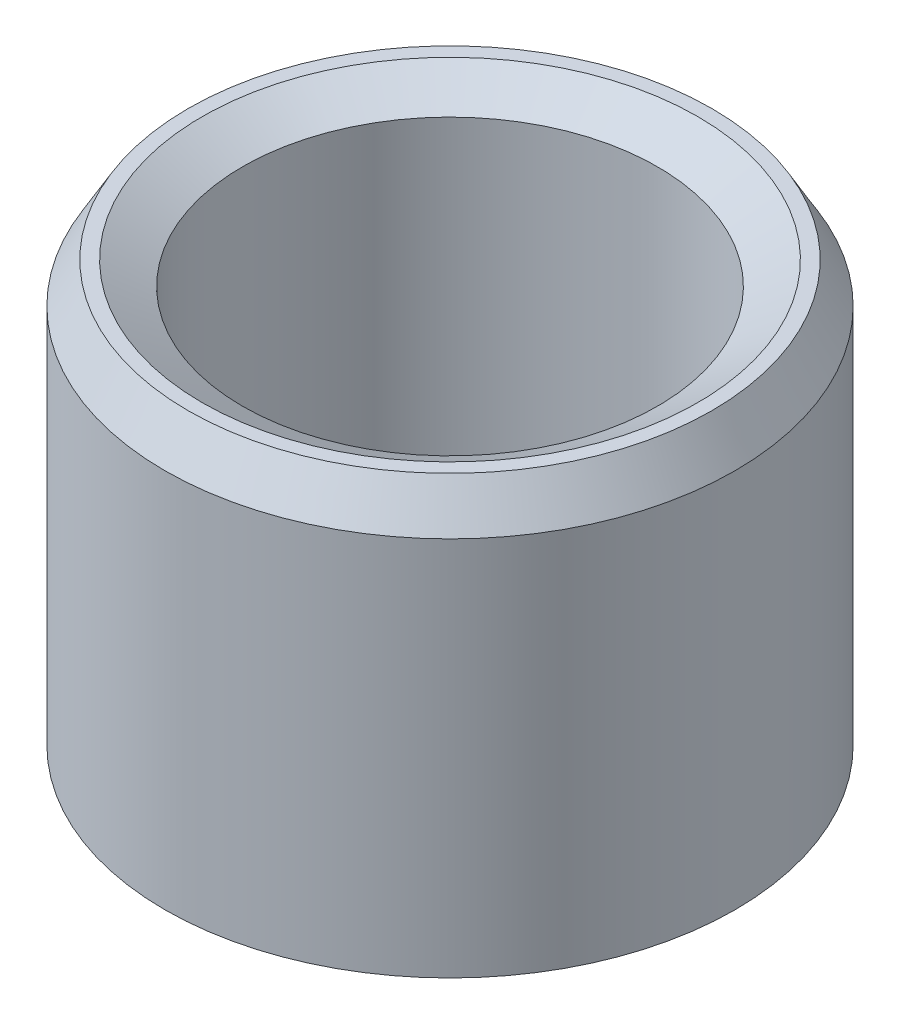
SolidWorks part; units mm, degrees
ref_plane "Front Plane" through (0, 0, 0) normal (0, 0, 1) x (1, 0, 0)
ref_plane "Top Plane" through (0, 0, 0) normal (0, 1, 0) x (1, 0, 0)
ref_plane "Right Plane" through (0, 0, 0) normal (1, 0, 0) x (0, 0, -1)
sketch "Sketch1" plane through (0, 0, 0) normal (0, 1, 0) x (1, 0, 0)
  circle A0 centre (0, 0) radius 12.5
  dimension "SLEEVE_OD" = 25
extrude "Boss-Extrude1" add sketch "Sketch1" along normal blind 19.4621
sketch "Sketch2" plane through (0, 0, 0) normal (0, 1, 0) x (1, 0, 0)
  circle A0 centre (0, 0) radius 9.0976
  dimension "BORE_D" = 18.1953
extrude "Cut-Extrude1" cut sketch "Sketch2" along normal through all
chamfer "Chamfer1" distance 1.7675 angle 30 4 edges at (0, 19.4621, 9.0976) (0, 0, 9.0976) (0, 0, 12.5) (0, 19.4621, 12.5) first distance on face at (0, 19.4621, 9.0976) first distance on face at (0, 0, 9.0976) first distance on face at (0, 19.4621, 12.5)
